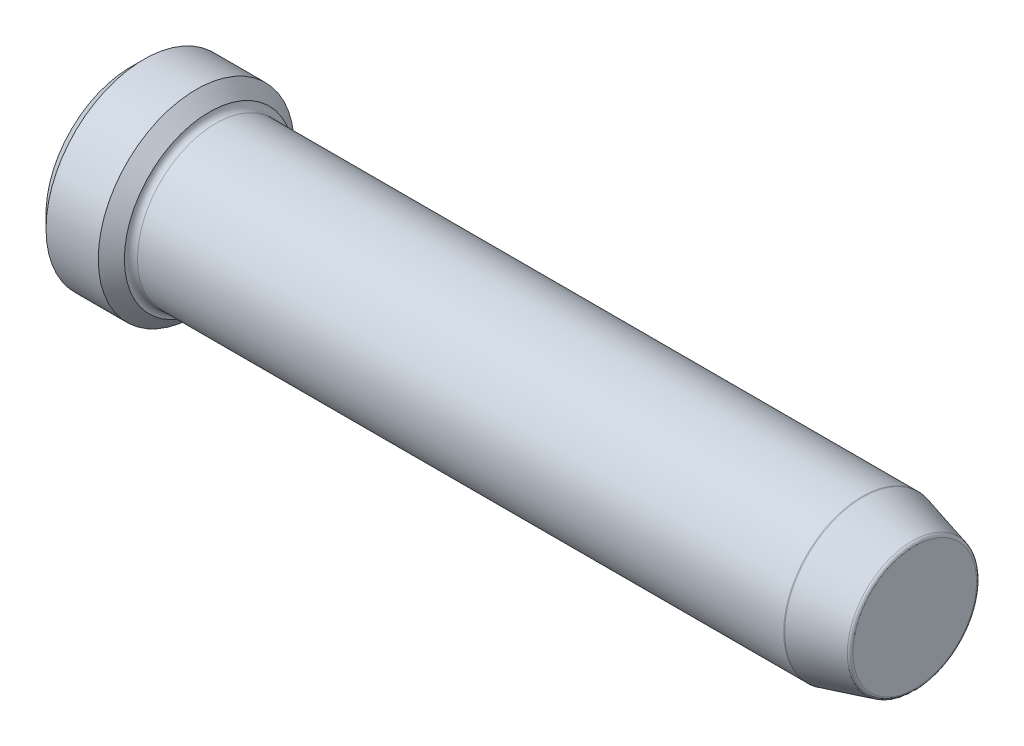
SolidWorks part; units mm, degrees
ref_plane "前视基准面" through (0, 0, 0) normal (0, 0, 1) x (1, 0, 0)
ref_plane "上视基准面" through (0, 0, 0) normal (0, 1, 0) x (1, 0, 0)
ref_plane "右视基准面" through (0, 0, 0) normal (1, 0, 0) x (0, 0, -1)
sketch "草图1" plane through (0, 0, 0) normal (0, 0, 1) x (1, 0, 0)
  line L0 (-70.6544, 0) -> (71.7013, 0) construction
  line L1 (0, 0) -> (0, 7.5)
  line L2 (0, 7.5) -> (6, 7.5)
  line L3 (6, 7.5) -> (6, 6)
  line L4 (56, 6) -> (60, 4.9282)
  line L5 (6, 6) -> (15, 6)
  line L6 (60, 4.9282) -> (60, 0)
  line L7 (0, 0) -> (60, 0)
  line L8 (15, 6) -> (56, 6)
  dimension "D1" = 15
  dimension "h" = 6
  dimension "D2" = 15
  dimension "D" = 12
  dimension "D3" = 4
  dimension "L" = 60
  dimension "L1" = 15
sketch "草图2" plane through (0, 0, 0) normal (0, 0, 1) x (1, 0, 0)
  line L0 (0, 0) -> (0, 7.5)
  line L1 (0, 7.5) -> (6, 7.5)
  line L2 (6, 7.5) -> (6, 6)
  line L3 (6, 6) -> (56, 6)
  line L4 (56, 6) -> (60, 4.9282)
  line L5 (60, 4.9282) -> (60, 0)
  line L6 (60, 0) -> (0, 0)
revolve "旋转1" add sketch "草图2" angle 360 about L0
chamfer "倒角1" distance 1 angle 45 2 edges at (6, 0, 7.5) (0, 0, 7.5)
fillet "圆角1" radius 0.5 1 edges at (6, 0, 6)
fillet "圆角2" radius 0.25 2 edges at (60, 0, 4.9282) (56, 0, 6)
